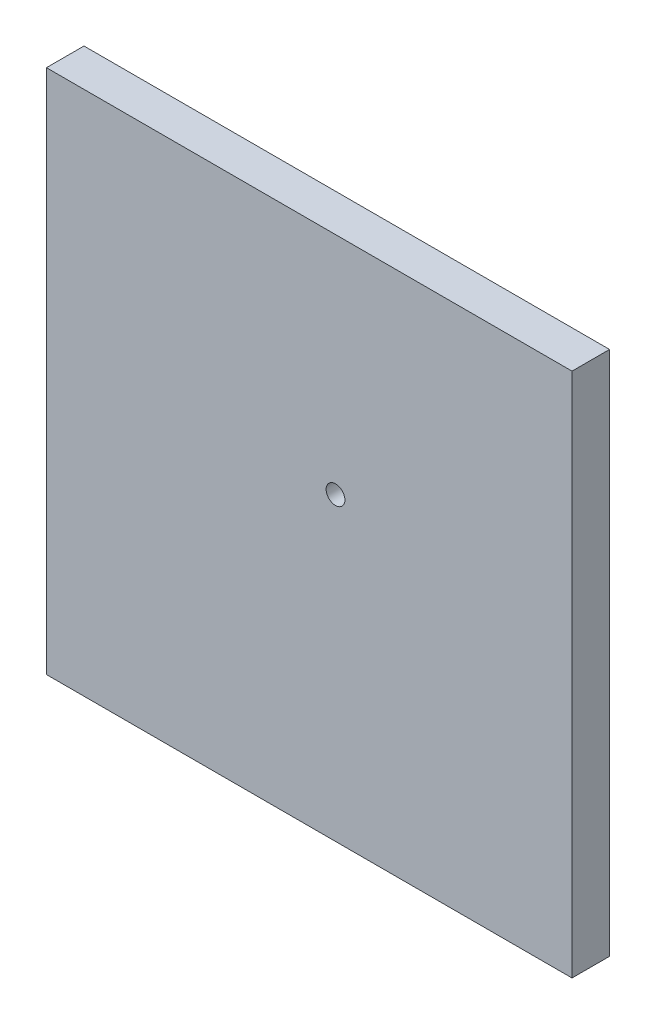
SolidWorks part; units mm, degrees
ref_plane "Front Plane" through (0, 0, 0) normal (0, 0, 1) x (1, 0, 0)
ref_plane "Top Plane" through (0, 0, 0) normal (0, 1, 0) x (1, 0, 0)
ref_plane "Right Plane" through (0, 0, 0) normal (1, 0, 0) x (0, 0, -1)
sketch "Sketch1" plane through (0, 0, 0) normal (0, 0, 1) x (1, 0, 0)
  line L1 (0, 0) -> (177.8, 0)
  line L2 (0, 0) -> (0, -177.8)
  line L3 (0, -177.8) -> (177.8, -177.8)
  line L4 (177.8, 0) -> (177.8, -177.8)
  dimension "D1" = 177.8
  dimension "D2" = 177.8
extrude "Boss-Extrude1" add sketch "Sketch1" along normal blind 12.7
sketch "Sketch2" plane through (0, 0, 12.7) normal (0, 0, 1) x (1, 0, 0)
  line L4 (0, 0) -> (0, -177.8)
  line L5 (0, -177.8) -> (177.8, -177.8)
  line L6 (177.8, -177.8) -> (177.8, 0)
  line L7 (177.8, 0) -> (0, 0)
  line L8 (0, 0) -> (0, -177.8)
  line L9 (0, -177.8) -> (177.8, -177.8)
  line L10 (177.8, -177.8) -> (177.8, 0)
  line L11 (177.8, 0) -> (0, 0)
  circle A0 centre (97.79, -76.2) radius 3.175
  dimension "D3" = 6.35
  dimension "D2" = 97.79
  dimension "D4" = 101.6
  dimension "D1" = 0
extrude "Cut-Extrude3" cut sketch "Sketch2" against normal through all contours A0
